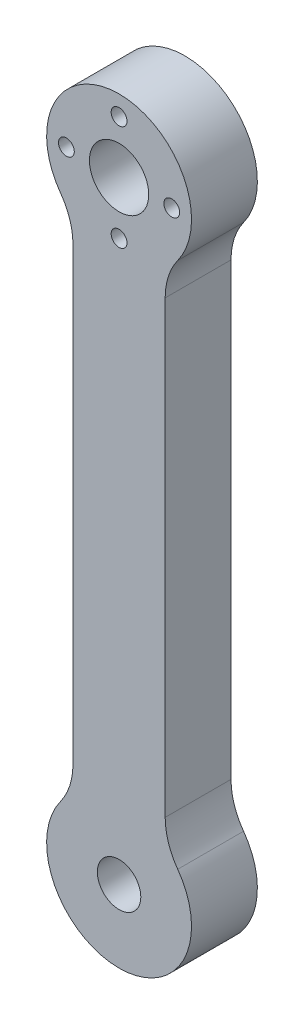
SolidWorks part; units mm, degrees
ref_plane "Plan de face" through (0, 0, 0) normal (0, 0, 1) x (1, 0, 0)
ref_plane "Plan de dessus" through (0, 0, 0) normal (0, 1, 0) x (1, 0, 0)
ref_plane "Plan de droite" through (0, 0, 0) normal (1, 0, 0) x (0, 0, -1)
sketch "Esquisse1" plane through (0, 0, 0) normal (0, 0, 1) x (1, 0, 0)
  line L0 (0, 21.7205) -> (0, -6.0998) construction
  line L1 (-7, 38) -> (-7, -38)
  line L2 (7, 38) -> (7, -38)
  line L3 (-8.714, 0) -> (6.1966, 0) construction
  arc A0 (7, 38) -> (-7, 38) centre (0, 46.4853) ccw
  arc A1 (7, -38) -> (-7, -38) centre (0, -46.4853) cw
  circle A2 centre (0, 46.4853) radius 4.5026
  point P11 (-7, 0)
  dimension "D3" = 11
  dimension "D1" = 76
  dimension "D2" = 14
extrude "Boss.-Extru.1" add sketch "Esquisse1" along normal blind 10
sketch "Esquisse8" plane through (0, 0, 10) normal (0, 0, 1) x (1, 0, 0)
  circle A0 centre (0, 46.4853) radius 8
  arc A1 (7, 38) -> (-7, 38) centre (0, 46.4853) ccw construction
  point P8 (0, 54.4853)
  point P10 (8, 46.4853)
  point P12 (0, 38.4853)
  point P14 (-8, 46.4853)
  dimension "D1" = 16
hole_wizard "Dégagement M21" positions "Esquisse8" profile "Esquisse7" hole size "M2" standard "ISO" end condition through all
sketch "Esquisse7" plane through (-8, 46.4853, 10) normal (1, 0, 0) x (0, -1, 0)
  line L0 (0, 0) -> (0, 10)
  line L1 (0, 10) -> (1.2, 10)
  line L2 (1.2, 10) -> (1.2, 0)
  line L5 (1.2, 0) -> (0, 0)
  line L11 (0, -6.35) -> (0, 107.95) construction
  dimension "Diamètre du perçage jusqu'au prochain" = 2.4
  dimension "Profondeur du perçage jusqu'au prochain" = 10
fillet "Congé1" radius 10 4 edges at (-7, -38, 5) (7, -38, 5) (7, 38, 5) (-7, 38, 5)
sketch "Esquisse9" plane through (0, 0, 10) normal (0, 0, 1) x (1, 0, 0)
  circle A0 centre (0, -46.4853) radius 5
  arc A1 (-8.9048, -40.0273) -> (8.9048, -40.0273) centre (0, -46.4853) ccw construction
  point P0 (0, -46.4853)
  dimension "D1" = 10
hole_wizard "Dégagement M61" positions "Esquisse9" profile "Esquisse10" hole size "M6" standard "ISO" end condition through all
sketch "Esquisse10" plane through (0, -46.4853, 10) normal (1, 0, 0) x (0, -1, 0)
  line L0 (0, 0) -> (0, 10)
  line L1 (0, 10) -> (3.3, 10)
  line L2 (3.3, 10) -> (3.3, 0)
  line L5 (3.3, 0) -> (0, 0)
  line L11 (0, -6.35) -> (0, 107.95) construction
  dimension "Diamètre du perçage jusqu'au prochain" = 6.6
  dimension "Profondeur du perçage jusqu'au prochain" = 10
equation "\"L1\" = 76mm"
equation "\"D1@Esquisse1\"=\"L1\""
